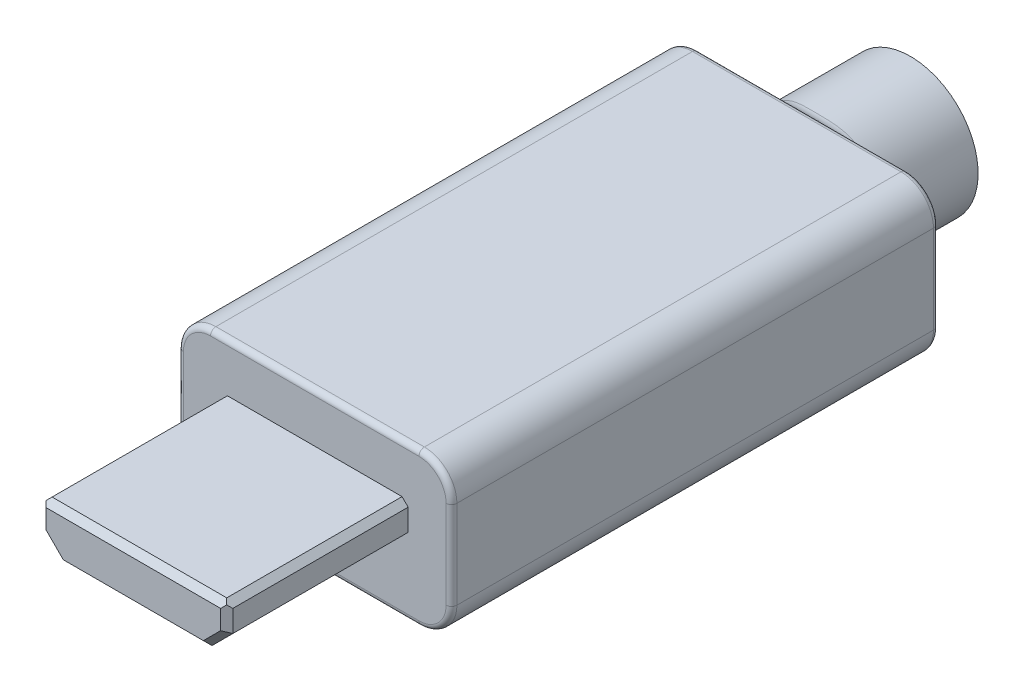
SolidWorks part; units mm, degrees
ref_plane "Front Plane" through (0, 0, 0) normal (0, 0, 1) x (1, 0, 0)
ref_plane "Top Plane" through (0, 0, 0) normal (0, 1, 0) x (1, 0, 0)
ref_plane "Right Plane" through (0, 0, 0) normal (1, 0, 0) x (0, 0, -1)
sketch "Sketch1" plane through (0, 0, 0) normal (0, 0, 1) x (1, 0, 0)
  line L0 (0, 0) -> (0, 1.8) construction
  line L1 (3.45, 1.8) -> (-3.45, 1.8)
  line L2 (-3.45, 1.8) -> (-3.45, 0.77)
  line L3 (-3.45, 0.77) -> (-2.68, 0)
  line L4 (-2.68, 0) -> (2.68, 0)
  line L5 (3.45, 0.77) -> (2.68, 0)
  line L6 (3.45, 1.8) -> (3.45, 0.77)
  dimension "D1" = 1.03
  dimension "D2" = 1.8
  dimension "D3" = 3.45
  dimension "D4" = 135
extrude "Boss-Extrude1" add sketch "Sketch1" along normal blind 6.7
chamfer "Chamfer1" distance 0.225 angle 45 6 edges at (0, 0, 6.7) (-3.065, 0.385, 6.7) (-3.45, 1.285, 6.7) (0, 1.8, 6.7) (3.45, 1.285, 6.7) (3.065, 0.385, 6.7)
chamfer "Chamfer2" distance 0.225 angle 45 2 edges at (-3.45, 1.8, 3.2375) (3.45, 1.8, 3.2375)
sketch "Sketch2" plane through (0, 0, 0) normal (0, 0, -1) x (-1, 0, 0)
  line L0 (0, 0.77) -> (0, 0) construction
  line L1 (3.85, 3.6) -> (-3.85, 3.6)
  line L2 (5.05, 2.4) -> (5.05, -0.86)
  line L3 (3.85, -2.06) -> (-3.85, -2.06)
  line L4 (-5.05, 2.4) -> (-5.05, -0.86)
  line L5 (5.05, 3.6) -> (-5.05, -2.06) construction
  line L6 (5.05, -2.06) -> (-5.05, 3.6) construction
  line L7 (-3.45, 0.77) -> (0, 0.77) construction
  line L8 (-3.225, 1.8) -> (3.225, 1.8) construction
  line L9 (-3.45, 0.77) -> (-3.45, 1.575) construction
  arc A0 (-3.85, -2.06) -> (-5.05, -0.86) centre (-3.85, -0.86) cw
  arc A1 (5.05, -0.86) -> (3.85, -2.06) centre (3.85, -0.86) cw
  arc A2 (3.85, 3.6) -> (5.05, 2.4) centre (3.85, 2.4) cw
  arc A3 (-3.85, 3.6) -> (-5.05, 2.4) centre (-3.85, 2.4) ccw
  point P0 (0, 0.77)
  dimension "D3" = 1.2
  dimension "D1" = 1.8
  dimension "D2" = 1.6
extrude "Boss-Extrude2" add sketch "Sketch2" along normal blind 18
fillet "Fillet1" radius 0.2 16 edges at (-4.6985, 3.2485, 0) (-5.05, 0.77, 0) (-4.6985, -1.7085, 0) (0, -2.06, 0) (4.6985, -1.7085, 0) (5.05, 0.77, 0) (4.6985, 3.2485, 0) (5.05, 0.77, -18) (4.6985, 3.2485, -18) (0, 3.6, -18) (-4.6985, 3.2485, -18) (-5.05, 0.77, -18) (-4.6985, -1.7085, -18) (0, -2.06, -18) (4.6985, -1.7085, -18) (0, 3.6, 0)
sketch "Sketch3" plane through (0, 0, -18) normal (0, 0, -1) x (-1, 0, 0)
  line L0 (0, 0.77) -> (0, 0) construction
  line L1 (-4.6985, 3.2485) -> (4.6985, -1.7085) construction
  circle A0 centre (0, 0.77) radius 2.5
  arc A1 (-3.85, 3.6) -> (-5.05, 2.4) centre (-3.85, 2.4) ccw construction
  arc A2 (3.85, -2.06) -> (5.05, -0.86) centre (3.85, -0.86) ccw construction
  dimension "D1" = 5
extrude "Boss-Extrude3" add sketch "Sketch3" along normal blind 4 and the other way blind 4
fillet "Fillet2" radius 0.6 1 edges at (2.5, 0.77, -18)
